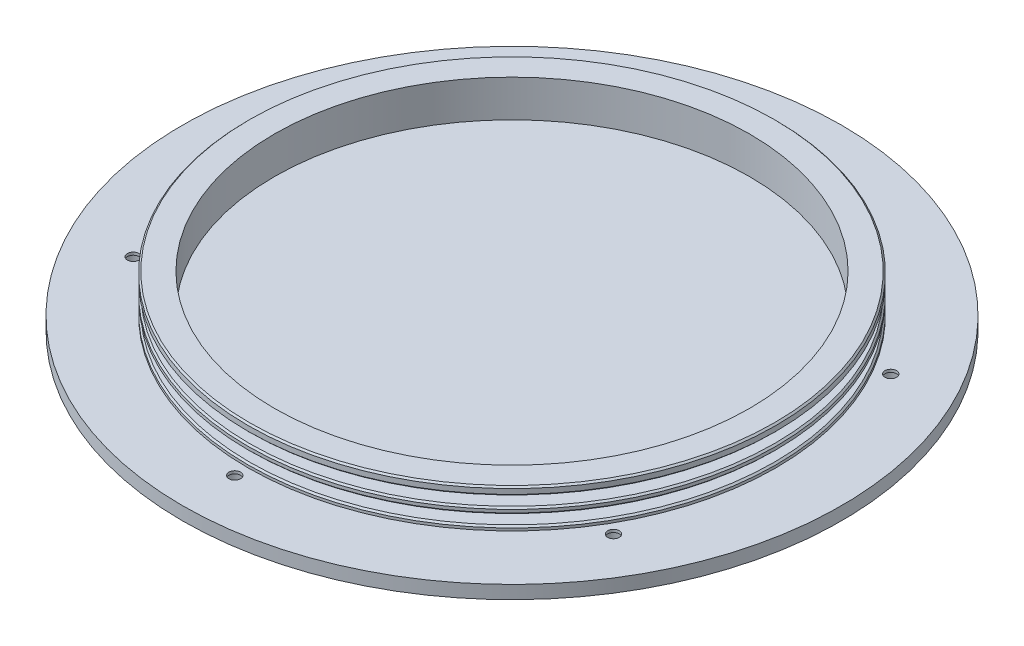
SolidWorks part; units mm, degrees
material "Glass"
ref_plane "Front Plane" through (0, 0, 0) normal (0, 0, 1) x (1, 0, 0)
ref_plane "Top Plane" through (0, 0, 0) normal (0, 1, 0) x (1, 0, 0)
ref_plane "Right Plane" through (0, 0, 0) normal (1, 0, 0) x (0, 0, -1)
sketch "Sketch1" plane through (0, 0, 0) normal (0, 1, 0) x (1, 0, 0)
  circle A0 centre (0, 0) radius 79.248
  dimension "D1" = 158.496
extrude "Extrude1" add sketch "Sketch1" along normal blind 3.175
ref_point "Point1"
sketch "Sketch2" plane through (0, 3.175, 0) normal (0, 1, 0) x (-1, 0, 0)
  circle A0 centre (0, 0) radius 63.5
extrude "Extrude2" add sketch "Sketch2" along normal blind 9.2075
sketch "Sketch4" plane through (0, 0, 0) normal (1, 0, 0) x (0, 0, -1)
  line L0 (-63.5, 12.3825) -> (-63.5, 3.175) construction
  line L1 (-63.5, 10.4051) -> (-59.69, 10.4051)
  line L2 (-63.5, 10.4051) -> (-63.5, 8.0429)
  line L3 (-63.5, 8.0429) -> (-59.69, 8.0429)
  line L4 (-59.69, 10.4051) -> (-59.69, 8.0429)
  line L5 (0, 0) -> (0, 13.8799) construction
  line L6 (-63.5, 6.5416) -> (-59.69, 6.5416)
  line L7 (-63.5, 6.5416) -> (-63.5, 4.1794)
  line L8 (-63.5, 4.1794) -> (-59.69, 4.1794)
  line L9 (-59.69, 6.5416) -> (-59.69, 4.1794)
  line L10 (-79.248, 0) -> (79.248, 0) construction
  dimension "D1" = 2.3622
  dimension "D2" = 2.3622
  dimension "D3" = 59.69
revolve "Cut-Revolve7" cut sketch "Sketch4" angle 360 about L5
sketch "Sketch6" plane through (0, 0, 0) normal (0, -1, 0) x (1, 0, 0)
  line L0 (0, 0) -> (0, 79.248) construction
  line L1 (0, 0) -> (0, -79.248) construction
  line L2 (0, 0) -> (68.6308, 39.624) construction
  line L3 (0, 0) -> (68.6308, -39.624) construction
  line L4 (0, 0) -> (-68.6308, -39.624) construction
  line L5 (0, 0) -> (-68.6308, 39.624) construction
  circle A0 centre (0, 0) radius 79.248 construction
chamfer "Chamfer1" distance 0.381 angle 45 5 edges at (0, 12.3825, 63.5) (0, 4.1794, -63.5) (0, 6.5416, -63.5) (0, 8.0429, -63.5) (0, 10.4051, -63.5)
sketch "Sketch7" plane through (0, 12.3825, 0) normal (0, 1, 0) x (-1, 0, 0)
  line L0 (0, 0) -> (0, 38.4938) construction
sketch "Sketch8" plane through (0, 12.3825, 0) normal (0, 1, 0) x (1, 0, 0)
  circle A0 centre (0, 0) radius 57.15
  dimension "D1" = 114.3
extrude "Cut-Extrude1" cut sketch "Sketch8" against normal blind 8.89
ref_axis "Axis1" through (0, 53.3427, 0) along (0, -1, 0)
ref_axis "Axis2" through (0, -73.9686, 0) along (0, 1, 0)
hole_wizard "CBORE for #3 Socket Head Cap Screw1" positions "3DSketch1" profile "Sketch5" counterbore size "#3" standard "Ansi Inch" end condition through all
sketch3d "3DSketch1"
  line L0 (0, -73.9686, 0) -> (0, 0, 0) construction
  point P4 (57.7422, 0, 33.3375)
  dimension "D1" = 66.675
sketch "Sketch5" plane through (57.7422, 0, 33.3375) normal (1, 0, 0) x (0, 0, -1)
  line L0 (0, 0) -> (0, 12.3825)
  line L1 (0, 12.3825) -> (1.397, 12.3825)
  line L3 (1.397, 12.3825) -> (1.397, 2.5146)
  line L4 (1.397, 2.5146) -> (2.5794, 2.5146)
  line L5 (2.5794, 2.5146) -> (2.5794, 0)
  line L7 (2.5794, 0) -> (0, 0)
  line L11 (0, -6.35) -> (0, 107.95) construction
  dimension "Thru Hole Dia." = 2.794
  dimension "Thru Hole Depth" = 12.3825
  dimension "C'Bore Dia." = 5.1587
  dimension "C'Bore Depth" = 2.5146
pattern_circular "CirPattern1" count 6 every 60 about axis through (0, -73.9686, 0) along (0, 1, 0) of "CBORE for #3 Socket Head Cap Screw1"
